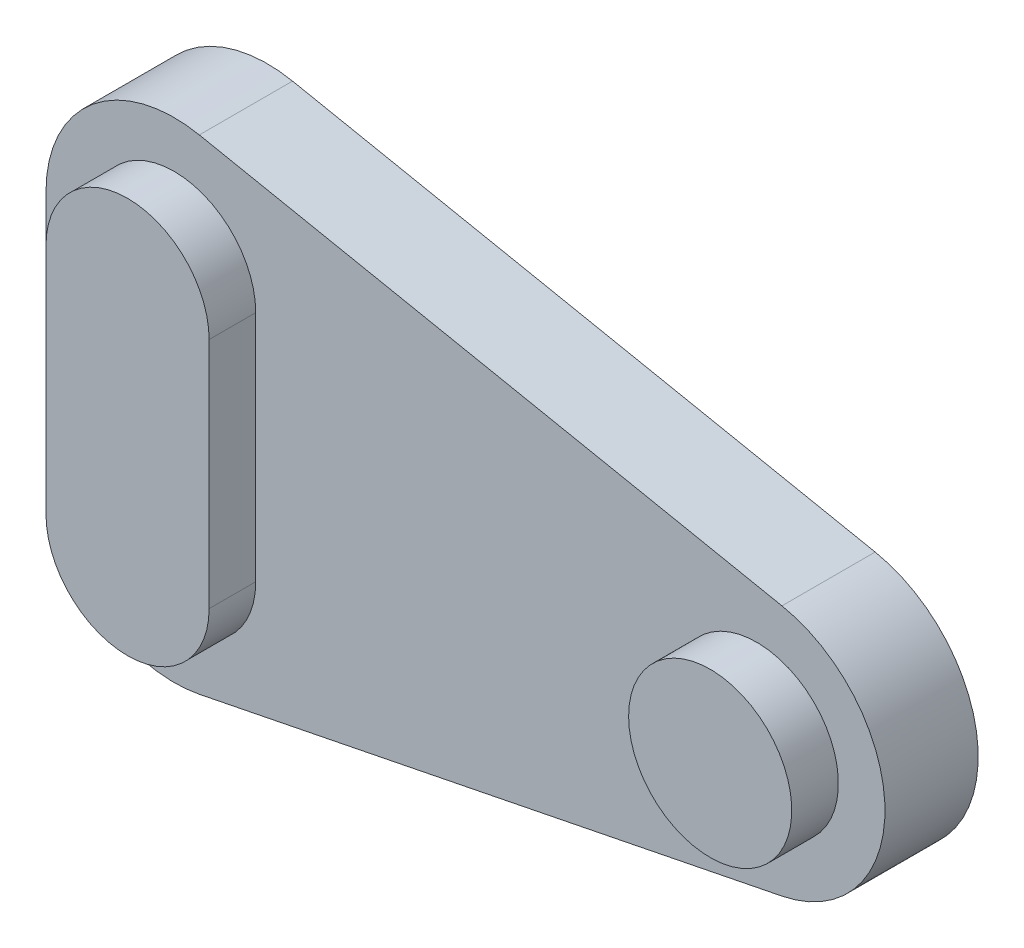
SolidWorks part; units mm, degrees
ref_plane "Front Plane" through (0, 0, 0) normal (0, 0, 1) x (1, 0, 0)
ref_plane "Top Plane" through (0, 0, 0) normal (0, 1, 0) x (1, 0, 0)
ref_plane "Right Plane" through (0, 0, 0) normal (1, 0, 0) x (0, 0, -1)
sketch "Sketch1" plane through (0, 0, 0) normal (0, 0, 1) x (1, 0, 0)
  line L0 (0, 0) -> (0, 12.7) construction
  line L1 (-4.445, 0) -> (-4.445, 12.7)
  line L2 (4.445, 0) -> (4.445, 12.7)
  line L3 (0, 0) -> (0, 12.7) construction
  line L4 (-6.985, 0) -> (-6.985, 12.7)
  line L6 (1.3699, 19.5494) -> (33.1199, 13.1994)
  line L7 (1.3699, -6.8494) -> (33.1199, -0.4994)
  arc A0 (-4.445, 0) -> (4.445, 0) centre (0, 0) ccw
  arc A1 (4.445, 12.7) -> (-4.445, 12.7) centre (0, 12.7) ccw
  circle A2 centre (31.75, 6.35) radius 4.445
  arc A3 (-6.985, 0) -> (1.3699, -6.8494) centre (0, 0) ccw
  arc A4 (1.3699, 19.5494) -> (-6.985, 12.7) centre (0, 12.7) ccw
  arc A5 (33.1199, -0.4994) -> (33.1199, 13.1994) centre (31.75, 6.35) ccw
  point P3 (0, 6.35)
  point P8 (0, 6.35)
  point P13 (0, 0)
  point P16 (0, 0)
  point P18 (-6.985, 6.35)
  dimension "D2" = 4.445
  dimension "D3" = 31.75
  dimension "D4" = 6.985
  dimension "D5" = 8.89
  dimension "D6" = 6.985
  dimension "D7" = 6.985
  dimension "D8" = 12.7
  dimension "D1" = 12.7
extrude "Boss-Extrude1" add sketch "Sketch1" along normal blind 5.08
extrude "Boss-Extrude2" add sketch "Sketch1<8>" along normal blind 7.62 contours L2 A1 L1 A0 | A2 region at (0, 6.35, 0) region at (31.75, 6.35, 0)
sketch "Sketch1<8>" plane through (0, 0, 0) normal (0, 0, 1) x (1, 0, 0) same geometry as "Sketch1"
